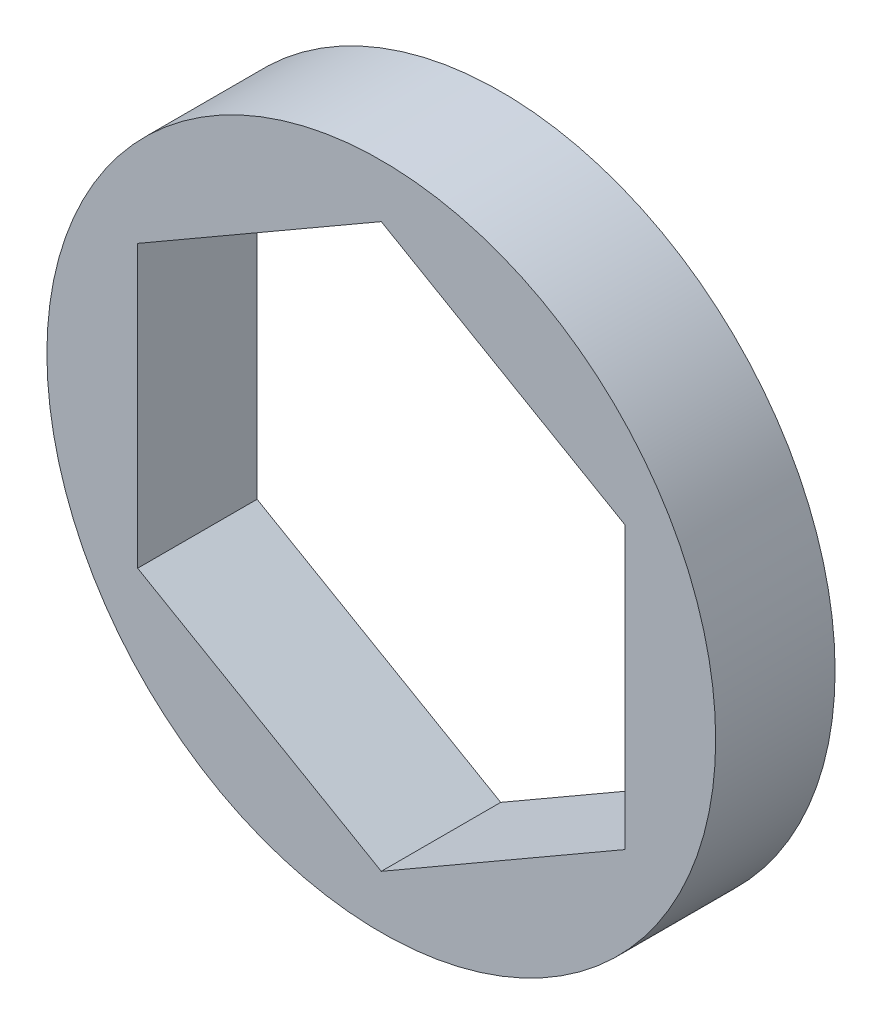
SolidWorks part; units mm, degrees
ref_plane "Front" through (0, 0, 0) normal (0, 0, 1) x (1, 0, 0)
ref_plane "Top" through (0, 0, 0) normal (0, 1, 0) x (1, 0, 0)
ref_plane "Right" through (0, 0, 0) normal (1, 0, 0) x (0, 0, -1)
sketch "Sketch1" plane through (0, 0, 0) normal (0, 0, 1) x (1, 0, 0)
  line L1 (0, 7.479) -> (-6.477, 3.7395)
  line L2 (-6.477, 3.7395) -> (-6.477, -3.7395)
  line L3 (-6.477, -3.7395) -> (0, -7.479)
  line L4 (0, -7.479) -> (6.477, -3.7395)
  line L5 (6.477, -3.7395) -> (6.477, 3.7395)
  line L6 (6.477, 3.7395) -> (0, 7.479)
  circle A0 centre (0, 0) radius 8.89
  circle A1 centre (0, 0) radius 6.477 construction
  dimension "D2" = 17.78
  dimension "D1" = 12.954
extrude "Boss-Extrude1" add sketch "Sketch1" along normal blind 3.175
